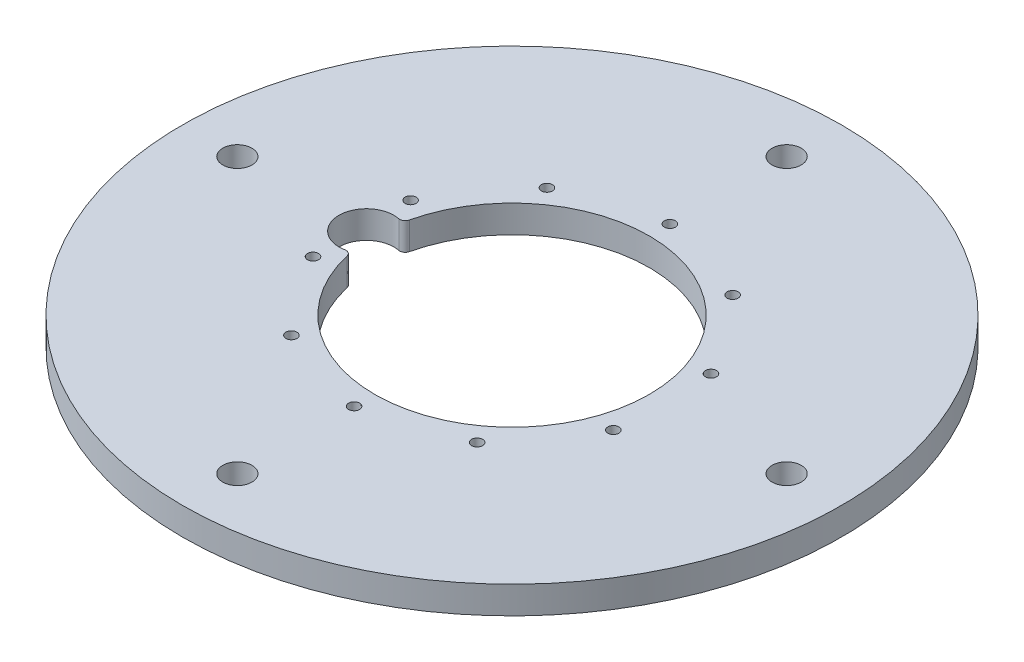
SolidWorks part; units mm, degrees
material "6061 Alloy"
ref_plane "Front Plane" through (0, 0, 0) normal (0, 0, 1) x (1, 0, 0)
ref_plane "Top Plane" through (0, 0, 0) normal (0, 1, 0) x (1, 0, 0)
ref_plane "Right Plane" through (0, 0, 0) normal (1, 0, 0) x (0, 0, -1)
sketch "Sketch1" plane through (0, 0, 0) normal (0, 1, 0) x (1, 0, 0)
  line L1 (0, 0) -> (0, 73.025) construction
  line L2 (0, 0) -> (0, 127) construction
  circle A3 centre (0, 0) radius 152.4
  circle A8 centre (0, 0) radius 127 construction
  circle A20 centre (0, 0) radius 63.5
  circle A23 centre (0, 0) radius 73.025 construction
  point P2 (0, 127)
  point P5 (0, 73.025)
  dimension "Diameter_Takeout_BoltCircle" = 254
  dimension "Diameter_ThrustPlate" = 304.8
  dimension "D2" = 146.05
  dimension "D4" = 127
  dimension "D1" = 0
extrude "ThrustPlate_TC3" add sketch "Sketch1" against normal blind 12.7 separate body contours A3 region at (-148.0895, 0, 0)
sketch "Sketch11" plane through (0, 0, 0) normal (0, 1, 0) x (1, 0, 0)
  point P0 (0, 127)
hole_wizard "UNDEF_Clearance_ThrustPlate" positions "Sketch11" profile "Sketch12" hole size "1/2" standard "ANSI Inch" end condition through all
sketch "Sketch12" plane through (0, 0, -127) normal (1, 0, 0) x (0, 0, 1)
  line L0 (0, 0) -> (0, 12.7)
  line L1 (0, 12.7) -> (6.7462, 12.7)
  line L2 (6.7462, 12.7) -> (6.7462, 0)
  line L5 (6.7462, 0) -> (0, 0)
  line L11 (0, -6.35) -> (0, 107.95) construction
  dimension "Thru Hole Dia." = 13.4925
  dimension "Thru Hole Depth" = 12.7
pattern_circular "Clearance_ThrustPlate_Pattern" count 4 over 360 about axis through (0, -12.7, 0) along (0, 1, 0) of "UNDEF_Clearance_ThrustPlate" reverse direction yes
sketch "Sketch22" plane through (0, 0, 0) normal (0, 1, 0) x (1, 0, 0)
  point P0 (0, 73.025)
hole_wizard "#10 Clearance Hole1" positions "Sketch22" profile "Sketch23" hole size "#10" standard "ANSI Inch" end condition through all
sketch "Sketch23" plane through (0, 0, -73.025) normal (1, 0, 0) x (0, 0, 1)
  line L0 (0, 0) -> (0, 12.7)
  line L1 (0, 12.7) -> (2.5527, 12.7)
  line L2 (2.5527, 12.7) -> (2.5527, 0)
  line L5 (2.5527, 0) -> (0, 0)
  line L11 (0, -6.35) -> (0, 107.95) construction
  dimension "Thru Hole Dia." = 5.1054
  dimension "Thru Hole Depth" = 12.7
pattern_circular "CirPattern1" count 10 over 360 about axis through (0, -12.7, 0) along (0, 1, 0) of "#10 Clearance Hole1" reverse direction yes
sketch "Sketch24" plane through (0, 0, 0) normal (0, 1, 0) x (1, 0, 0)
  line L0 (0, 0) -> (0, 152.4) construction
  line L1 (0, 0) -> (-152.4, 0) construction
  circle A0 centre (0, 0) radius 152.4 construction
  circle A1 centre (0, 0) radius 63.5 construction
  arc A3 (-64.8239, 12.4543) -> (-64.8239, -12.4543) centre (-67.31, 0) ccw
  arc A6 (-64.8239, 12.4543) -> (-61.8526, 14.3703) centre (-64.3267, 14.9452) ccw
  arc A7 (-61.8526, 14.3703) -> (-61.8526, -14.3703) centre (0, 0) ccw
  arc A8 (-64.8239, -12.4543) -> (-61.8526, -14.3703) centre (-64.3267, -14.9452) cw
  dimension "D2" = 12.7
  dimension "D4" = 2.54
  dimension "D1" = 67.31
  dimension "D3" = 90
extrude "Cut-Extrude1" cut sketch "Sketch24" against normal up to next
equation "\"Diameter_BackPlate\"= 6"
equation "\"VAR_Diameter_BackPlate_BoltCircle\"= 5.75"
equation "\"VAR_Diameter_FuelOuterPlenum\"= 4.4"
equation "\"Thickness_ThrustPlate\"= 0.5'undetermined"
equation "\"Diameter_ThrustPlate\"= 12'defined"
equation "\"Diameter_Takeout_BoltCicle\"= 10'defined"
equation "\"Diameter_Takeout_BoltCircle@Sketch1\"=\"Diameter_Takeout_BoltCicle\""
equation "\"Diameter_ThrustPlate@Sketch1\"=\"Diameter_ThrustPlate\""
equation "\"D1@ThrustPlate_TC3\"=\"Thickness_ThrustPlate\""
equation "\"VAR_Diameter_CBORE\"= 0.44'undetermined"
equation "\"VAR_Diameter_Clearance_ThrustPlate\"= 0.25'undetermined"
equation "\"NumberBolts_BackPlate\"= 20"
equation "\"NumberBolts_Takeout\"= 4'defined"
equation "\"D1@Clearance_ThrustPlate_Pattern\"=\"NumberBolts_Takeout\""
